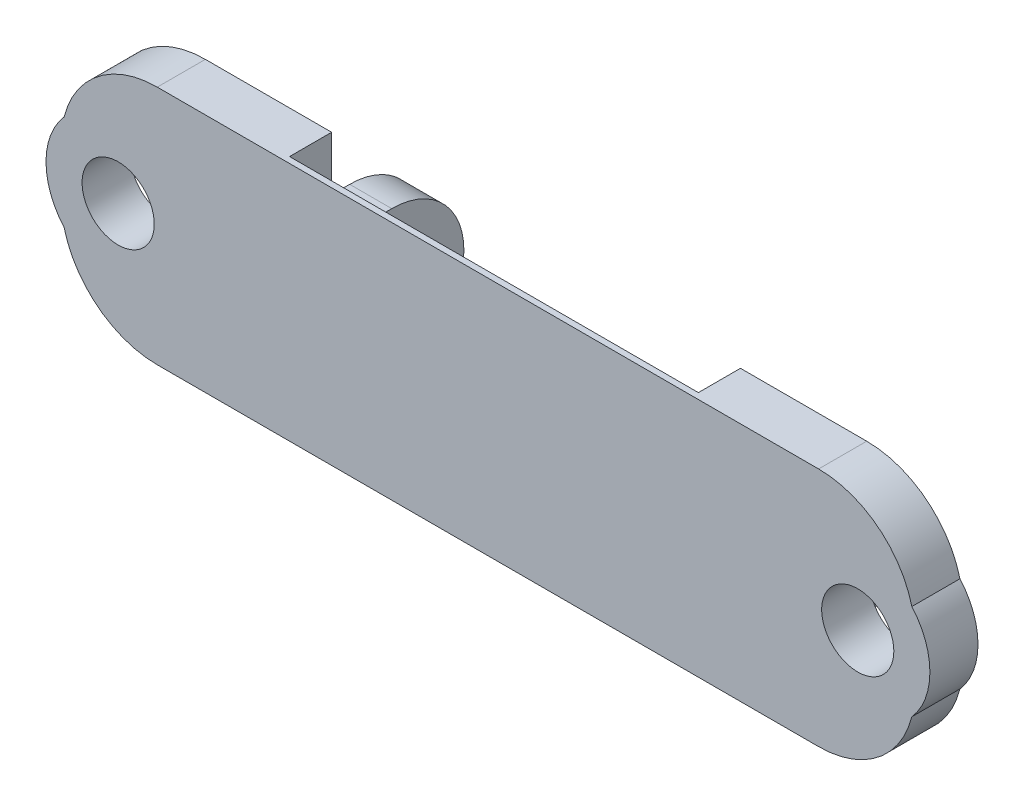
SolidWorks part; units mm, degrees
material "ABS"
ref_plane "Front Plane" through (0, 0, 0) normal (0, 0, 1) x (1, 0, 0)
ref_plane "Top Plane" through (0, 0, 0) normal (0, 1, 0) x (1, 0, 0)
ref_plane "Right Plane" through (0, 0, 0) normal (1, 0, 0) x (0, 0, -1)
sketch "Sketch1" plane through (0, 0, 0) normal (0, 0, 1) x (1, 0, 0)
  line L0 (8, 0) -> (63, 0)
  line L1 (0, 8) -> (0, 12) construction
  line L2 (8, 20) -> (63, 20)
  line L3 (71, 12) -> (71, 8) construction
  line L4 (35.5, 20) -> (35.5, 0) construction
  line L5 (18.5, 20) -> (52.5, 20)
  line L6 (18.5, 20) -> (18.5, 0)
  line L7 (18.5, 0) -> (52.5, 0)
  line L8 (52.5, 0) -> (52.5, 20)
  arc A0 (63, 0) -> (71, 8) centre (63, 8) ccw
  arc A1 (63, 20) -> (71, 12) centre (63, 12) cw
  arc A2 (0, 12) -> (8, 20) centre (8, 12) cw
  arc A3 (8, 0) -> (0, 8) centre (8, 8) cw
  circle A4 centre (4.746, 10) radius 3
  arc A5 (0.246, 13.9686) -> (0.246, 6.0314) centre (4.746, 10) ccw
  circle A6 centre (66.254, 10) radius 3
  arc A7 (70.754, 13.9686) -> (70.754, 6.0314) centre (66.254, 10) cw
  point P8 (71, 0)
  point P13 (0, 20)
  point P16 (0, 0)
  dimension "D3" = 8
  dimension "D6" = 6
  dimension "D7" = 12
  dimension "D1" = 71
  dimension "D2" = 20
  dimension "D4" = 3.254
  dimension "D5" = 10
  dimension "D8" = 34
  dimension "D9" = 17
extrude "Boss-Extrude3" add sketch "Sketch1" against normal blind 4 contours A5 A3 L0 L6 L2 A2 A4 | A7 A1 L2 L8 L0 A0 A6 region at (10.088, 10, 0) region at (60.912, 10, 0)
extrude "Boss-Extrude4" add sketch "Sketch1<9>" against normal blind 2 contours L0 L8 L2 L6 region at (35.5, 10, 0)
sketch "Sketch1<9>" plane through (0, 0, 0) normal (0, 0, 1) x (1, 0, 0) same geometry as "Sketch1"
sketch "Sketch2" plane through (18.5, 0, 0) normal (1, 0, 0) x (0, 0, -1)
  line L0 (2, 20) -> (0.5, 20)
  line L1 (0.5, 20) -> (2, 7.7072)
  line L2 (2, 20) -> (2, 0) construction
  line L3 (2, 7.7072) -> (2, 20)
  dimension "D1" = 1.5
  dimension "D2" = 12.2928
extrude "Cut-Extrude1" cut sketch "Sketch2" along normal blind 34
sketch "Sketch3" plane through (18.5, 0, 0) normal (1, 0, 0) x (0, 0, -1)
  line L0 (4, 0) -> (9, 0)
  line L2 (9, 12) -> (4, 12)
  line L3 (4, 20) -> (4, 0) construction
  line L4 (4, 12) -> (4, 0)
  arc A0 (9, 0) -> (9, 12) centre (9, 6) ccw
  circle A1 centre (9, 6) radius 3
  dimension "D1" = 6
  dimension "D2" = 6
  dimension "D3" = 7
  dimension "D4" = 7
extrude "Boss-Extrude5" add sketch "Sketch3" against normal blind 3.5
ref_plane "Plane1" through (35.5, 0, 0) normal (1, 0, 0) x (0, 0, -1)
mirror "Mirror1" about plane through (35.5, 0, 0) normal (1, 0, 0) of "Boss-Extrude5"
